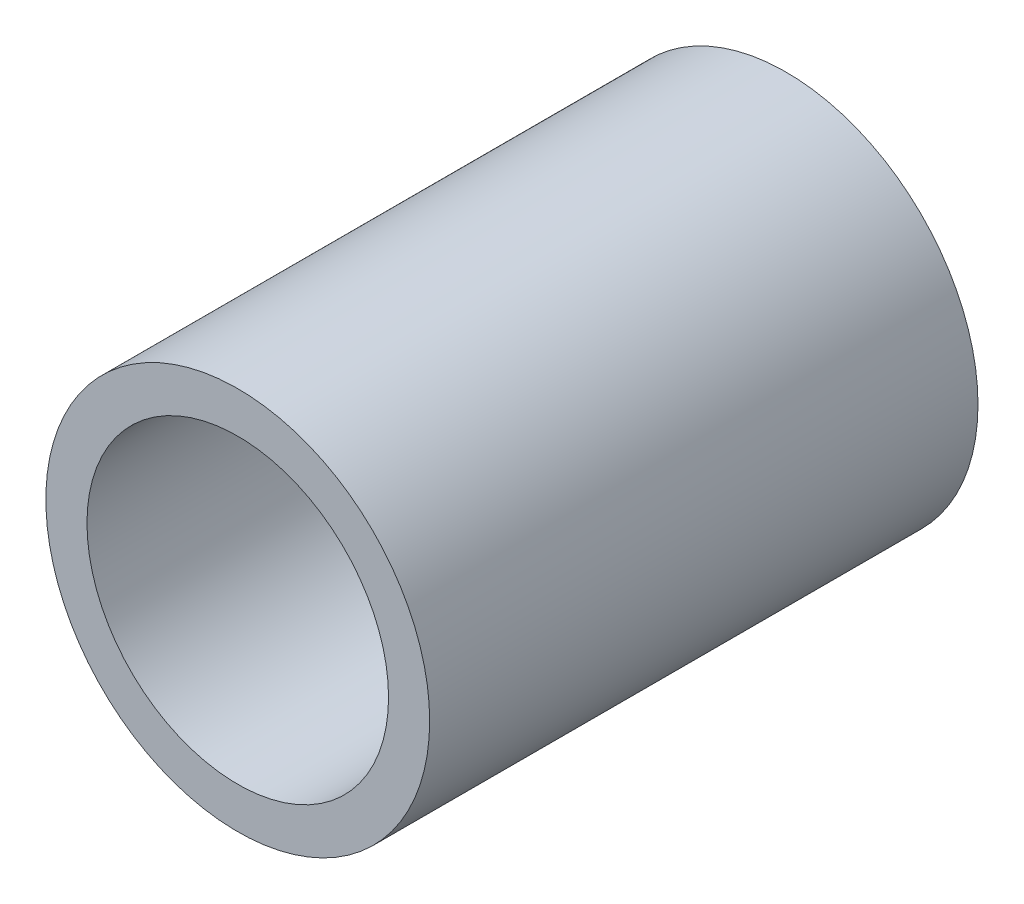
SolidWorks part; units mm, degrees
ref_plane "Front Plane" through (0, 0, 0) normal (0, 0, 1) x (1, 0, 0)
ref_plane "Top Plane" through (0, 0, 0) normal (0, 1, 0) x (1, 0, 0)
ref_plane "Right Plane" through (0, 0, 0) normal (1, 0, 0) x (0, 0, -1)
sketch "Sketch2" plane through (0, 0, 6.9643) normal (0, 0, 1) x (1, 0, 0)
  circle A3 centre (234.2949, 5.2797) radius 1.6 construction
  circle A4 centre (234.2949, 5.2797) radius 1.6
  circle A5 centre (234.2949, 5.2797) radius 1.8
  circle A6 centre (234.2949, 5.2797) radius 3.5
  circle A7 centre (234.2949, 5.2797) radius 2.75
  dimension "D1" = 0.2
  dimension "D2" = 7
  dimension "D3" = 5.5
  dimension "D4" = 3.2
extrude "Boss-Extrude1" add sketch "Sketch2" along normal blind 10 contours A7 | A6
extrude "Boss-Extrude2" add sketch "Sketch2<3>" along normal blind 3 contours A7 A5 region at (231.6227, 5.2797, 6.9643)
sketch "Sketch2<3>" plane through (0, 0, 6.9643) normal (0, 0, 1) x (1, 0, 0) same geometry as "Sketch2"
